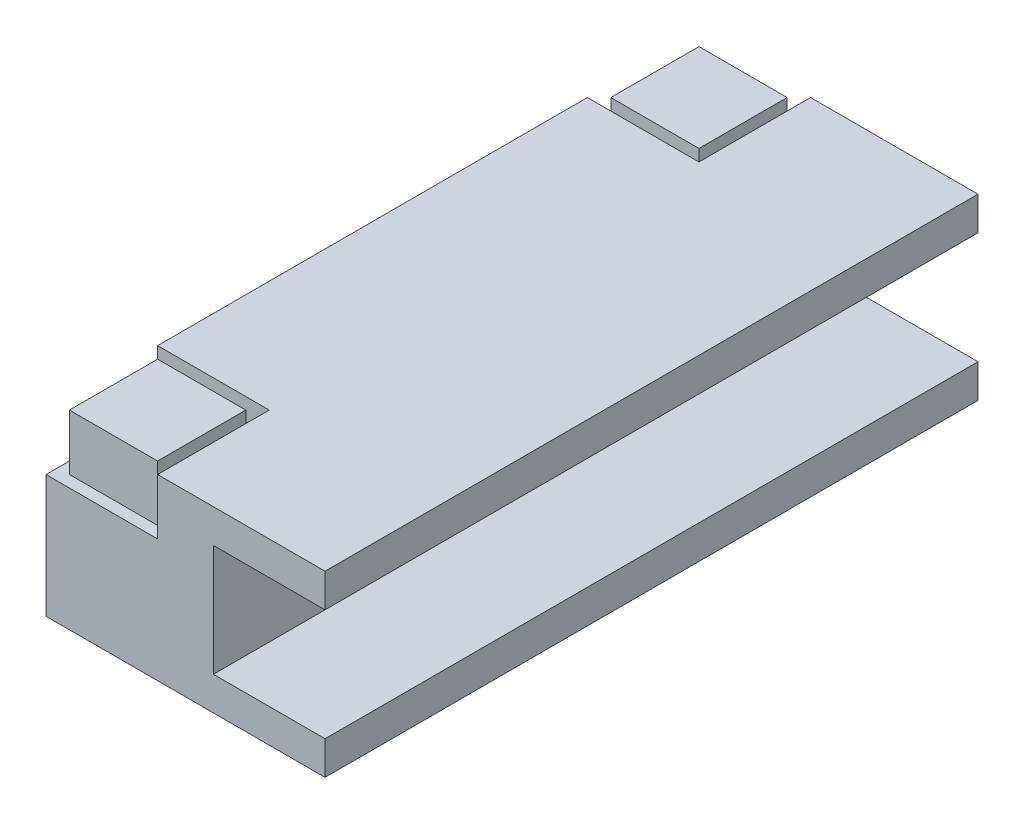
SolidWorks part; units mm, degrees
ref_plane "Płaszczyzna przednia" through (0, 0, 0) normal (0, 0, 1) x (1, 0, 0)
ref_plane "Płaszczyzna górna" through (0, 0, 0) normal (0, 1, 0) x (1, 0, 0)
ref_plane "Płaszczyzna prawa" through (0, 0, 0) normal (1, 0, 0) x (0, 0, -1)
sketch "Szkic1" plane through (0, 0, 0) normal (0, 0, 1) x (1, 0, 0)
  line L0 (10, -10) -> (10, -16)
  line L1 (-10, -10) -> (10, -10)
  line L2 (-10, -10) -> (-10, 10)
  line L3 (-10, 10) -> (10, 10)
  line L4 (10, -10) -> (10, 10)
  line L5 (-10, -10) -> (10, 10) construction
  line L6 (-10, 10) -> (10, -10) construction
  line L7 (10, -16) -> (-40, -16)
  line L8 (-40, -16) -> (-40, 16)
  line L9 (-40, 16) -> (10, 16)
  line L10 (10, 16) -> (10, 10)
  point P0 (0, 0)
  dimension "D1" = 20
  dimension "D2" = 50
  dimension "D3" = 6
  dimension "D4" = 32
extrude "Dodanie-wyciągnięcie1" add sketch "Szkic1" along normal blind 117 contours L10 L9 L8 L7 L0 L1 L2 L3 region at (-20, 0, 0)
sketch "Szkic2" plane through (0, 16, 0) normal (0, 1, 0) x (1, 0, 0)
  line L1 (-40, -117) -> (-20, -117)
  line L2 (-40, -117) -> (-40, -97)
  line L3 (-40, -97) -> (-20, -97)
  line L4 (-20, -117) -> (-20, -97)
  line L5 (-40, 0) -> (-20, 0)
  line L6 (-40, 0) -> (-40, -20)
  line L7 (-40, -20) -> (-20, -20)
  line L8 (-20, 0) -> (-20, -20)
  dimension "D1" = 20
  dimension "D2" = 20
extrude "Wytnij-wyciągnięcie1" cut sketch "Szkic2" against normal blind 10
sketch "Szkic3" plane through (0, 6, 0) normal (0, 1, 0) x (1, 0, 0)
  line L0 (-40, 0) -> (-40, -20) construction
  line L1 (-40, -20) -> (-20, -20) construction
  line L2 (-20, -20) -> (-20, 0) construction
  line L3 (-20, 0) -> (-40, 0) construction
  line L4 (-40, -97) -> (-40, -117) construction
  line L5 (-40, -117) -> (-20, -117) construction
  line L6 (-20, -117) -> (-20, -97) construction
  line L7 (-20, -97) -> (-40, -97) construction
  line L8 (-40, 0) -> (-40, -20)
  line L9 (-40, -20) -> (-20, -20)
  line L10 (-20, -20) -> (-20, 0)
  line L11 (-20, 0) -> (-40, 0)
  line L12 (-40, -97) -> (-40, -117)
  line L13 (-40, -117) -> (-20, -117)
  line L14 (-20, -117) -> (-20, -97)
  line L15 (-20, -97) -> (-40, -97)
  line L16 (-37.9, -2.1) -> (-37.9, -17.9)
  line L17 (-37.9, -17.9) -> (-22.1, -17.9)
  line L18 (-22.1, -17.9) -> (-22.1, -2.1)
  line L19 (-22.1, -2.1) -> (-37.9, -2.1)
  line L28 (-37.9, -99.1) -> (-37.9, -114.9)
  line L29 (-37.9, -114.9) -> (-22.1, -114.9)
  line L30 (-22.1, -114.9) -> (-22.1, -99.1)
  line L31 (-22.1, -99.1) -> (-37.9, -99.1)
  line L32 (-37.9, -99.1) -> (-37.9, -114.9)
  line L33 (-37.9, -114.9) -> (-22.1, -114.9)
  line L34 (-22.1, -114.9) -> (-22.1, -99.1)
  line L35 (-22.1, -99.1) -> (-37.9, -99.1)
  dimension "D1" = 2.1
  dimension "D2" = 2.1
extrude "Dodanie-wyciągnięcie2" add sketch "Szkic3" along normal blind 10 contours L34 L35 L32 L33 | L18 L19 L16 L17 region at (-30, 6, 10) region at (-30, 6, 107)
sketch "Szkic4" plane through (0, -16, 0) normal (0, -1, 0) x (1, 0, 0)
  line L0 (-10, 117) -> (-10, 0) construction
  line L1 (-10, 117) -> (-10, 0)
  line L2 (-40, 117) -> (-40, 0) construction
  line L3 (-19.6, 63.7) -> (-30, 63.7)
  line L4 (-19.6, 63.7) -> (-19.6, 53.3)
  line L5 (-19.6, 53.3) -> (-30, 53.3)
  line L6 (-30, 63.7) -> (-30, 53.3)
  point P6 (-40, 58.5)
  point P7 (-30, 58.5)
  dimension "D1" = 10.4
  dimension "D2" = 10
extrude "Wytnij-wyciągnięcie2" cut sketch "Szkic4" against normal blind 15 contours L3 L6 L5 L4 region at (-24.8, -16, 58.5)
